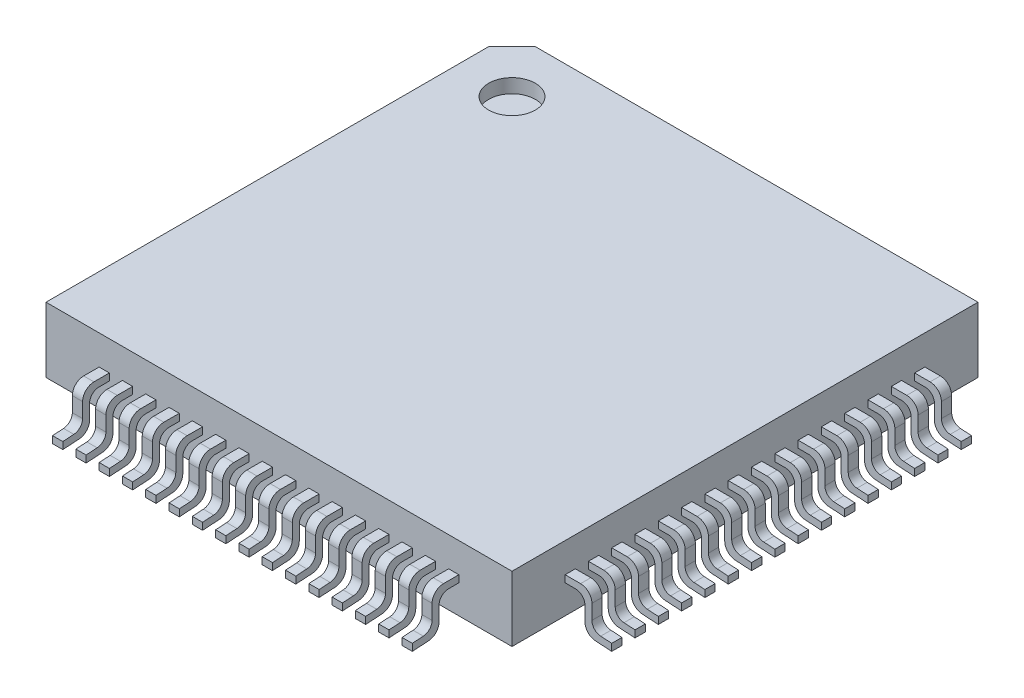
SolidWorks part; units mm, degrees
note: '?' marks a value the reader was unsure of.
ref_plane "Plano frontal" through (0, 0, 0) normal (0, 0, 1) x (1, 0, 0)
ref_plane "Plano superior" through (0, 0, 0) normal (0, 1, 0) x (1, 0, 0)
ref_plane "Plano direito" through (0, 0, 0) normal (1, 0, 0) x (0, 0, -1)
ref_plane "Body_Plane" through (0, 0.16, 0) normal (0, 1, 0) x (-1, 0, 0)
sketch "Sketch2" plane through (0, 0.16, 0) normal (0, 1, 0) x (1, 0, 0)
  line L1 (5, -5) -> (-5, -5)
  line L2 (5, -5) -> (5, 5)
  line L3 (5, 5) -> (-5, 5)
  line L4 (-5, -5) -> (-5, 5)
  line L5 (5, -5) -> (-5, 5) construction
  line L6 (5, 5) -> (-5, -5) construction
  point P0 (0, 0)
  dimension "D1" = 10
  dimension "D2" = 10
extrude "Body" add sketch "Sketch2" along normal blind 1.4
ref_plane "Lead_1_Plane" through (0, 0, 3.75) normal (0, 0, 1) x (1, 0, 0)
sketch "Sketch3" plane through (0, 0, 3.75) normal (0, 0, 1) x (1, 0, 0)
  line L0 (5, 1.56) -> (5, 0) construction
  line L1 (6, 1.5239) -> (6, 0) construction
  line L2 (5, 0.925) -> (5.3311, 0.925)
  line L3 (5, 0.775) -> (5.225, 0.775)
  line L4 (5.425, 0.575) -> (5.425, 0.2616)
  line L5 (5.6511, 0.0213) -> (6, 0)
  line L6 (5, 0) -> (6, 0) construction
  line L7 (5.575, 0.6811) -> (5.575, 0.3644)
  line L8 (5.7628, 0.1648) -> (6, 0.1503)
  line L9 (6, 0.1503) -> (6, 0)
  line L10 (5, 0.775) -> (5, 0.925)
  line L11 (5, 1.56) -> (5, 0.16) construction
  line L12 (-5, 0.16) -> (5, 0.16) construction
  line L13 (7.454, -0.0889) -> (7.7699, -0.1082) construction
  line L14 (7.6535, 0.0492) -> (7.8703, 0.0359) construction
  arc A0 (5.225, 0.775) -> (5.425, 0.575) centre (5.225, 0.575) cw
  arc A1 (5.425, 0.2616) -> (5.6511, 0.0213) centre (5.6657, 0.2616) ccw
  arc A2 (5.3311, 0.925) -> (5.575, 0.6811) centre (5.3311, 0.6811) cw
  arc A3 (5.575, 0.3644) -> (5.7628, 0.1648) centre (5.775, 0.3644) ccw
  point P8 (5.7628, 0.1648)
  point P21 (5, 0.86)
  point P28 (5.651, 0.0213)
  dimension "D3" = 0.2
  dimension "D4" = 0.2
  dimension "D11" = 0.15
  dimension "D9" = 0.15
  dimension "D1" = 1
  dimension "D2" = 3.5
  dimension "D5" = 0.575
  dimension "D6" = 0.15
  dimension "D7" = 0.15
  dimension "D8" = 0.085
  dimension "D10" = 0.15
  dimension "D12" = 0.16
  dimension "D13" = 0
  dimension "D14" = 0
extrude "Lead" add sketch "Sketch3" along normal mid plane 0.22
ref_axis "Axis1" through (0, 0.03, 0) along (0, 1, 0)?
pattern_linear "SD_Leads" count 16 spacing 0.5 along (0, 0, -1) of "Lead"
pattern_circular "CirPattern1" count 4 over 360 about axis through (0, 0, 0) along (0, 1, 0) of "SD_Leads", "Lead"
sketch "Sketch4" plane through (0, 1.56, 0) normal (0, 1, 0) x (1, 0, 0)
  line L0 (-5, 3.82) -> (-3.82, 3.82) construction
  line L1 (-5, 5) -> (-5, -5) construction
  line L2 (-3.82, 3.82) -> (-3.82, 5) construction
  line L3 (5, 5) -> (-5, 5) construction
  circle A0 centre (-3.82, 3.82) radius 0.5
extrude "Cut-Extrude1" cut sketch "Sketch4" against normal blind 0.3
chamfer "Chamfer1" distance 0.5 angle 45 1 edges at (-5, 0.86, -5)
equation "\"BODY_SIDE\"= 10"
equation "\"BODY_THICKNESS\"= 1.4"
equation "\"LEAD_BODY_OFFSET\"= 0.16"
equation "\"NUM_LEADS\"= 64"
equation "\"PITCH\"= 0.5"
equation "\"LEAD_WIDTH\"= 0.22"
equation "\"LEAD_THICKNESS\"= 0.15"
equation "\"LEAD_LENGTH\"= 1"
equation "\"D1@Sketch2\" = \"BODY_SIDE\""
equation "\"D2@Sketch2\" = \"BODY_SIDE\""
equation "\"D6@Sketch3\" = \"LEAD_THICKNESS\""
equation "\"D7@Sketch3\" = \"LEAD_THICKNESS\""
equation "\"D10@Sketch3\" = \"LEAD_THICKNESS\""
equation "\"D11@Sketch3\" = \"LEAD_THICKNESS\""
equation "\"D1@Sketch3\" = \"LEAD_LENGTH\""
equation "\"D1@LEAD\" = \"LEAD_WIDTH\""
equation "\"LEADS_SIDE\"= \"NUM_LEADS\" / 4"
equation "\"D1@Lead_1_Plane\" = ( \"BODY_SIDE\" - ( \"LEADS_SIDE\" * \"PITCH\" - \"PITCH\" + \"LEAD_WIDTH\" ) + \"LEAD_WIDTH\" ) / 2"
equation "\"D1@SD_Leads\" = \"LEADS_SIDE\""
equation "\"D3@SD_Leads\" = \"PITCH\""
equation "\"D1@Body\" = \"BODY_THICKNESS\""
equation "\"D1@Body_Plane\" = \"LEAD_BODY_OFFSET\""
equation "\"D12@Sketch3\" = \"LEAD_BODY_OFFSET\""
equation "\"D9@Sketch3\" = \"LEAD_THICKNESS\""
equation "\"D5@Sketch3\" = ( \"LEAD_LENGTH\" + \"LEAD_THICKNESS\" ) / 2"
